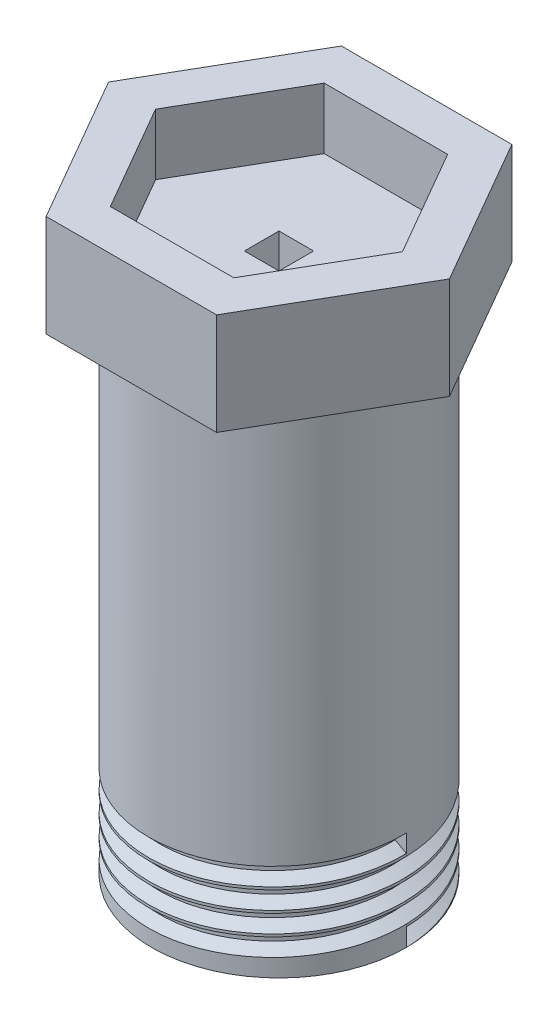
SolidWorks part; units mm, degrees
ref_plane "Front Plane" through (0, 0, 0) normal (0, 0, 1) x (1, 0, 0)
ref_plane "Top Plane" through (0, 0, 0) normal (0, 1, 0) x (1, 0, 0)
ref_plane "Right Plane" through (0, 0, 0) normal (1, 0, 0) x (0, 0, -1)
sketch "Sketch1" plane through (0, 0, 0) normal (0, 1, 0) x (1, 0, 0)
  circle A0 centre (0, 0) radius 6.25
  dimension "D1" = 12.5
extrude "Boss-Extrude1" add sketch "Sketch1" along normal blind 24.5
thread "Thread1" pitch 1 method cut profile "Thread Profile1" start angle 0, offset 0, length 4, pitch 1, diameter 12.5
ref_plane "Plane1" through (6.25, 0, 0) normal (0, 0, 1) x (1, 0, 0)
sketch "Thread Profile1" plane through (6.25, 0, 0) normal (0, 0, 1) x (1, 0, 0)
  line L0 (0, 0) -> (0, 1) construction
  line L11 (0, 0) -> (0, 0.875)
  line L12 (0, 0.875) -> (-0.5413, 0.5625)
  line L13 (-0.5413, 0.5625) -> (-0.5413, 0.3125)
  line L15 (-0.5413, 0.3125) -> (0, 0)
  line L17 (-0.5413, 0.4375) -> (0, 0.4375) construction
  point P2 (0, 0)
  dimension "Pitch" = 1
  dimension "Profile_Angle" = 60
  dimension "Profile_Land" = 0.25
  dimension "Profile_Height" = 0.5413
sketch "Sketch4" plane through (0, 24.5, 0) normal (0, 1, 0) x (1, 0, 0)
  line L1 (8.3716, 0) -> (4.1858, 7.25)
  line L2 (4.1858, 7.25) -> (-4.1858, 7.25)
  line L3 (-4.1858, 7.25) -> (-8.3716, 0)
  line L4 (-8.3716, 0) -> (-4.1858, -7.25)
  line L5 (-4.1858, -7.25) -> (4.1858, -7.25)
  line L6 (4.1858, -7.25) -> (8.3716, 0)
  circle A2 centre (0, 0) radius 7.25 construction
  circle A3 centre (0, 0) radius 6.25 construction
  dimension "D1" = 1
extrude "Boss-Extrude2" add sketch "Sketch4" along normal blind 5
sketch "Sketch5" plane through (0, 29.5, 0) normal (0, 1, 0) x (1, 0, 0)
  line L0 (8.3716, 0) -> (4.1858, 7.25) construction
  line L1 (3.0311, 5.25) -> (-3.0311, 5.25)
  line L2 (-3.0311, 5.25) -> (-6.0622, 0)
  line L3 (-6.0622, 0) -> (-3.0311, -5.25)
  line L4 (-3.0311, -5.25) -> (3.0311, -5.25)
  line L5 (3.0311, -5.25) -> (6.0622, 0)
  line L6 (6.0622, 0) -> (3.0311, 5.25)
  circle A0 centre (0, 0) radius 5.25 construction
  dimension "D1" = 2
extrude "Cut-Extrude1" cut sketch "Sketch5" against normal offset from surface (3 mm away) 2 up to face at (0, 24.5, 6.25)
sketch "Sketch6" plane through (0, 26.5, 0) normal (0, 1, 0) x (1, 0, 0)
  line L1 (-0.85, -0.85) -> (0.85, -0.85)
  line L2 (-0.85, -0.85) -> (-0.85, 0.85)
  line L3 (-0.85, 0.85) -> (0.85, 0.85)
  line L4 (0.85, -0.85) -> (0.85, 0.85)
  line L5 (-0.85, -0.85) -> (0.85, 0.85) construction
  line L6 (-0.85, 0.85) -> (0.85, -0.85) construction
  point P0 (0, 0)
  dimension "D1" = 1.7
  dimension "D2" = 1.7
extrude "Cut-Extrude2" cut sketch "Sketch6" against normal through all both and the other way through all
equation "\"diameter_electrode_outer\"= 13mm"
equation "\"height_thread\"= 4mm"
equation "\"D1@Sketch1\"=\"diameter_electrode_outer\"-\"offset\""
equation "\"D1@Boss-Extrude1\"=\"height_extrude_Cz\"+\"offset\"+\"height_thread\""
equation "\"diameter_tube\"= 2mm"
equation "\"offset\"= 0.5mm"
equation "\"height_turning_knob\"= 5mm"
equation "\"D1@Boss-Extrude2\"=\"height_turning_knob\""
equation "\"D1@Sketch5\"=2mm"
equation "\"width_dupont\" = 1.7mm"
equation "\"height_dupont\"= 1.7mm"
equation "\"length_dupont\"= 11.5mm"
equation "\"D1@Sketch6\"=\"width_dupont\""
equation "\"D2@Sketch6\"=\"width_dupont\""
equation "\"height_extrude_Cz\"= 20mm"
equation "\"D4@Thread1\"=\"height_thread\""
